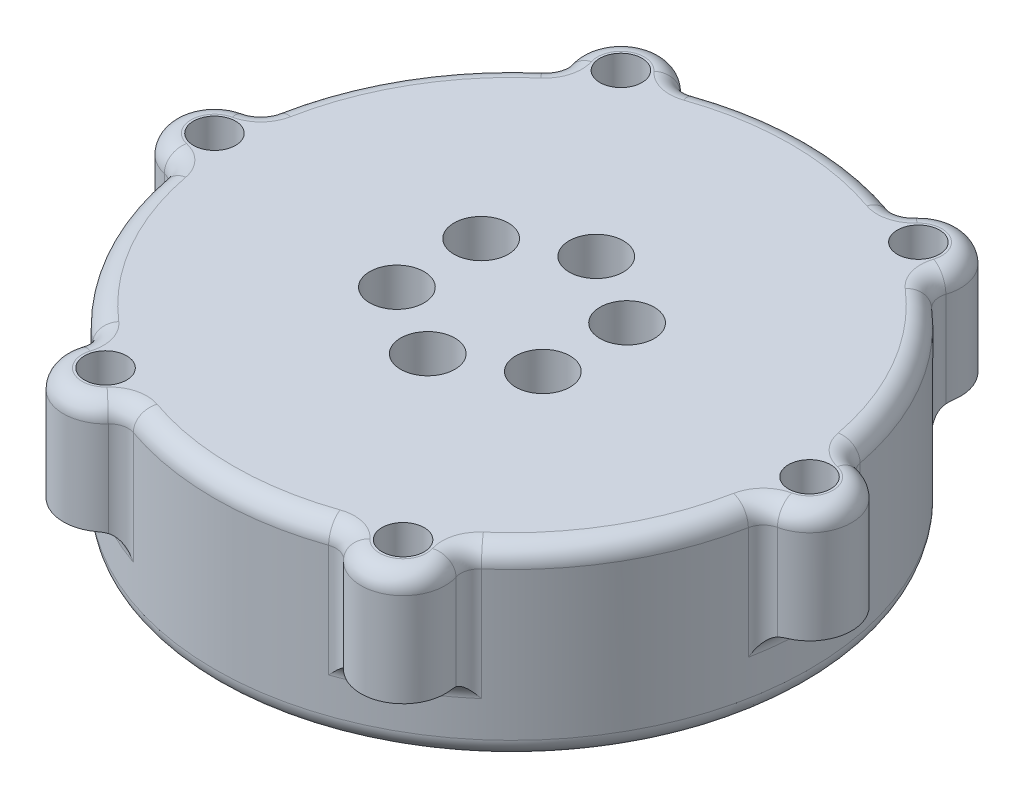
SolidWorks part; units mm, degrees
ref_plane "Front Plane" through (0, 0, 0) normal (0, 0, 1) x (1, 0, 0)
ref_plane "Top Plane" through (0, 0, 0) normal (0, 1, 0) x (1, 0, 0)
ref_plane "Right Plane" through (0, 0, 0) normal (1, 0, 0) x (0, 0, -1)
sketch "Sketch1" plane through (0, 0, 0) normal (0, 1, 0) x (1, 0, 0)
  circle A0 centre (0, 0) radius 28.78
  circle A1 centre (0, 0) radius 12.5
  circle A2 centre (0, 0) radius 31.78
  dimension "D1" = 25
  dimension "D2" = 57.56
  dimension "D3" = 3
extrude "Boss-Extrude1" add sketch "Sketch1" along normal blind 8 contours A2
extrude "Boss-Extrude2" add sketch "Sketch1<3>" against normal blind 11.8 contours A2 A0 region at (-30.8811, 0, 0)
sketch "Sketch1<3>" plane through (0, 0, 0) normal (0, 1, 0) x (1, 0, 0) same geometry as "Sketch1"
extrude "Boss-Extrude3" add sketch "Sketch1<5>" against normal blind 11 contours A1 region at (0, 0, 0)
sketch "Sketch1<5>" plane through (0, 0, 0) normal (0, 1, 0) x (1, 0, 0) same geometry as "Sketch1"
sketch "Sketch2" plane through (0, -11, 0) normal (0, -1, 0) x (1, 0, 0)
  circle A0 centre (0, 0) radius 9 construction
  circle A1 centre (0, 9) radius 1.25
  circle A2 centre (7.7942, 4.5) radius 1.25
  circle A3 centre (7.7942, -4.5) radius 1.25
  circle A4 centre (0, -9) radius 1.25
  circle A5 centre (-7.7942, -4.5) radius 1.25
  circle A6 centre (-7.7942, 4.5) radius 1.25
  circle A7 centre (0, 9) radius 2.9
  circle A8 centre (-7.7942, 4.5) radius 2.9
  circle A9 centre (-7.7942, -4.5) radius 2.9
  circle A10 centre (0, -9) radius 2.9
  circle A11 centre (7.7942, -4.5) radius 2.9
  circle A12 centre (7.7942, 4.5) radius 2.9
  point P17 (0, 0)
  dimension "D1" = 18
  dimension "D2" = 2.5
  dimension "D4" = 5.8
  dimension "D3" = 6
extrude "Cut-Extrude1" cut sketch "Sketch2" against normal through all contours A6 | A1 | A2 | A3 | A4 | A5 region at (0, -11, 9) region at (7.7942, -11, 4.5) region at (7.7942, -11, -4.5) region at (0, -11, -9) region at (-7.7942, -11, -4.5) region at (-7.7942, -11, 4.5)
extrude "Cut-Extrude2" cut sketch "Sketch2<3>" against normal through all from offset 4 offset against normal yes
sketch "Sketch2<3>" plane through (0, -11, 0) normal (0, -1, 0) x (1, 0, 0) same geometry as "Sketch2"
sketch "Sketch3" plane through (0, 8, 0) normal (0, 1, 0) x (1, 0, 0)
  circle A1 centre (0, 0) radius 31.78 construction
  arc A2 (-31.4614, 4.4887) -> (-31.4614, -4.4887) centre (-31.78, 0) ccw
  arc A3 (-31.4614, -4.4887) -> (-19.618, -25.002) centre (0, 0) ccw
  arc A4 (-11.8434, 29.4907) -> (-19.618, 25.002) centre (-15.89, 27.5223) ccw
  arc A5 (19.618, 25.002) -> (11.8434, 29.4907) centre (15.89, 27.5223) ccw
  arc A6 (31.4614, -4.4887) -> (31.4614, 4.4887) centre (31.78, 0) ccw
  arc A7 (11.8434, -29.4907) -> (19.618, -25.002) centre (15.89, -27.5223) ccw
  arc A8 (-19.618, -25.002) -> (-11.8434, -29.4907) centre (-15.89, -27.5223) ccw
  arc A9 (-19.618, 25.002) -> (-31.4614, 4.4887) centre (0, 0) ccw
  arc A10 (11.8434, 29.4907) -> (-11.8434, 29.4907) centre (0, 0) ccw
  arc A11 (31.4614, 4.4887) -> (19.618, 25.002) centre (0, 0) ccw
  arc A12 (-11.8434, -29.4907) -> (11.8434, -29.4907) centre (0, 0) ccw
  point P6 (0, 0)
  point P19 (0, 0)
  circle M7 centre (0, 0) radius 31.78
  dimension "D2" = 9
  dimension "D3" = 6
extrude "Boss-Extrude4" add sketch "Sketch3" against normal blind 12 contours A2 M7 | A4 M7 | A5 M7 | A6 M7 | A7 M7 | A8 M7 region at (-33.6313, 8, 0) region at (-16.8157, 8, -29.1256) region at (-16.8157, 8, 29.1256) region at (16.8157, 8, -29.1256) region at (16.8157, 8, 29.1256) region at (33.6313, 8, 0)
sketch "Sketch4" plane through (0, 8, 0) normal (0, 1, 0) x (1, 0, 0)
  circle A0 centre (-15.89, 27.5223) radius 2.25
  circle A1 centre (15.89, 27.5223) radius 2.25
  circle A2 centre (31.78, 0) radius 2.25
  circle A3 centre (15.89, -27.5223) radius 2.25
  circle A4 centre (-15.89, -27.5223) radius 2.25
  circle A5 centre (-31.78, 0) radius 2.25
  dimension "D1" = 4.5
extrude "Cut-Extrude3" cut sketch "Sketch4" against normal blind 10
fillet "Fillet1" radius 2 31 edges at (18.14, 8, 31.4194) (36.28, 8, 0) (18.14, 8, -31.4194) (-18.14, 8, -31.4194) (-36.28, 8, 0) (-18.14, 8, 31.4194) (0, -11.8, 31.78) (-11.8434, 2, 29.4907) (0, 8, 31.78) (11.8434, 2, 29.4907) (15.89, -4, 27.5223) (19.618, 2, 25.002) (27.5223, 8, 15.89) (31.4614, 2, 4.4887) (31.78, -4, 0) (31.4614, 2, -4.4887) (27.5223, 8, -15.89) (19.618, 2, -25.002) (15.89, -4, -27.5223) (11.8434, 2, -29.4907) (0, 8, -31.78) (-11.8434, 2, -29.4907) (-15.89, -4, -27.5223) (-19.618, 2, -25.002) (-27.5223, 8, -15.89) (-31.4614, 2, -4.4887) (-31.78, -4, 0) (-31.4614, 2, 4.4887) (-27.5223, 8, 15.89) (-19.618, 2, 25.002) (-15.89, -4, 27.5223)
